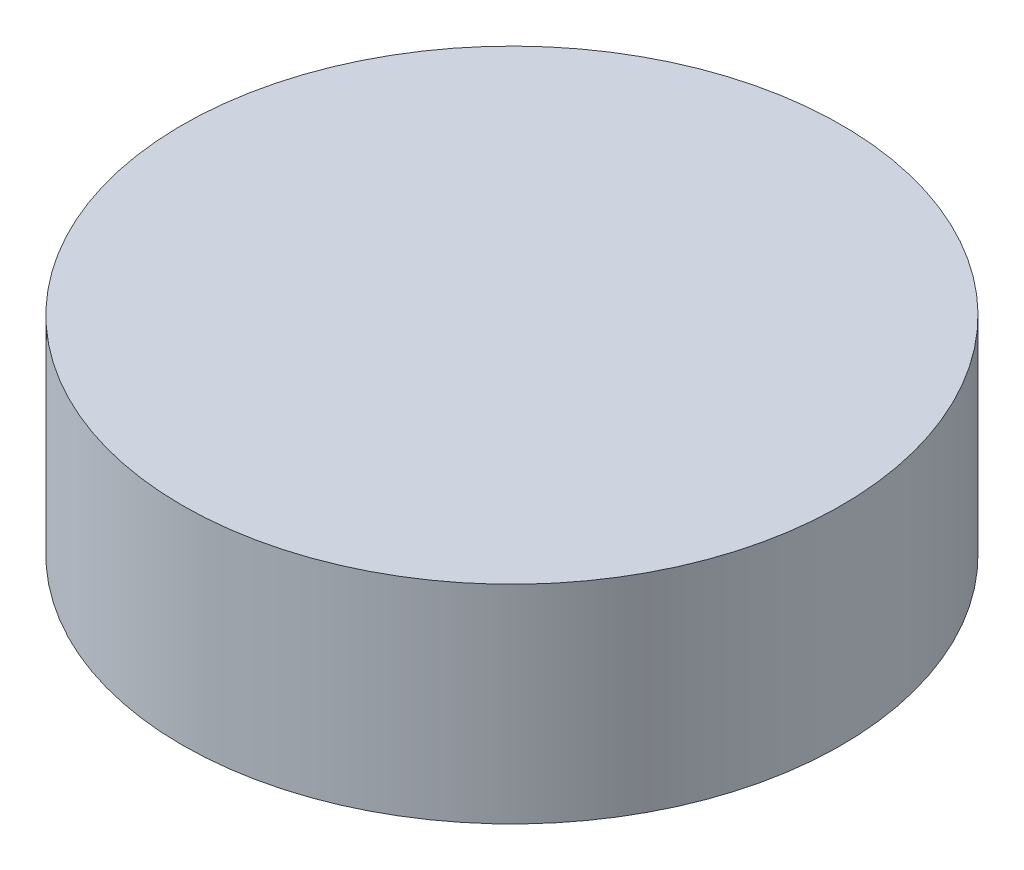
SolidWorks part; units mm, degrees
ref_plane "Front Plane" through (0, 0, 0) normal (0, 0, 1) x (1, 0, 0)
ref_plane "Top Plane" through (0, 0, 0) normal (0, 1, 0) x (1, 0, 0)
ref_plane "Right Plane" through (0, 0, 0) normal (1, 0, 0) x (0, 0, -1)
sketch "Sketch1" plane through (0, 0, 0) normal (0, 1, 0) x (1, 0, 0)
  circle A0 centre (0, 0) radius 6.35
  dimension "D1" = 12.7
extrude "Boss-Extrude1" add sketch "Sketch1" along normal blind 4 contours A0
sketch "Sketch2" plane through (0, 0, 0) normal (0, -1, 0) x (1, 0, 0)
  circle A0 centre (0, 0) radius 4.2
  circle A1 centre (0, 4.2) radius 1
  circle A2 centre (0, -4.2) radius 1
  dimension "D1" = 8.4
  dimension "D2" = 2
  dimension "D3" = 2
extrude "Cut-Extrude2" cut sketch "Sketch2" against normal blind 1 contours A2
extrude "Cut-Extrude3" cut sketch "Sketch2<3>" against normal blind 1 contours A0 | A1
sketch "Sketch2<3>" plane through (0, 0, 0) normal (0, -1, 0) x (1, 0, 0) same geometry as "Sketch2"
